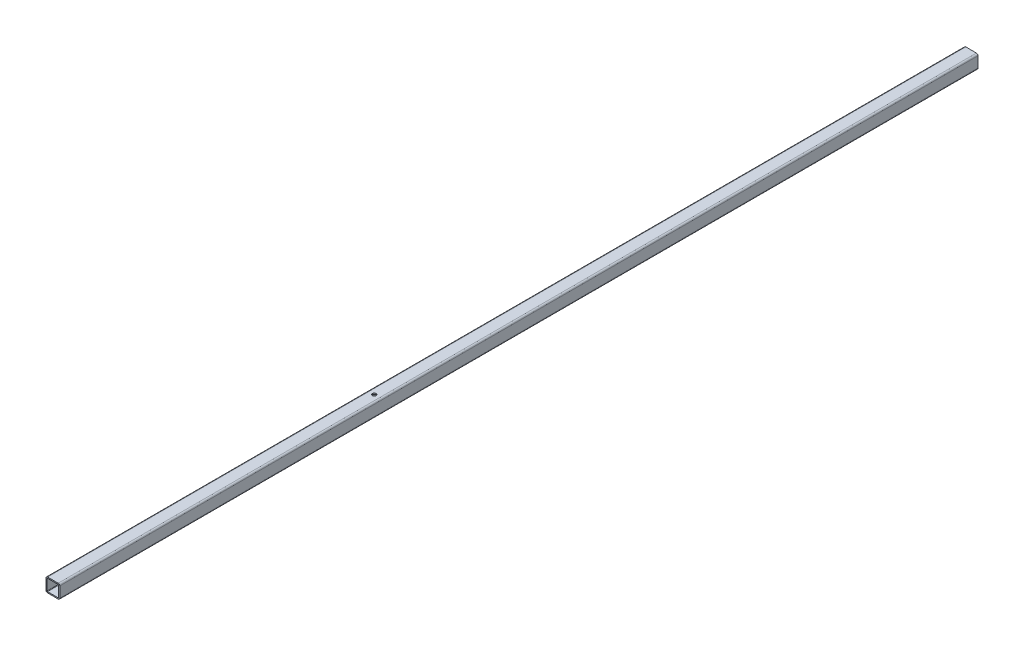
SolidWorks part; units mm, degrees
material "Plain Carbon Steel"
ref_plane "Front" through (0, 0, 0) normal (0, 0, 1) x (1, 0, 0)
ref_plane "Top" through (0, 0, 0) normal (0, 1, 0) x (1, 0, 0)
ref_plane "Right" through (0, 0, 0) normal (1, 0, 0) x (0, 0, -1)
ref_plane "Plane1" through (0, 0, 0) normal (0, 0, 1) x (1, 0, 0)
ref_axis "Axis1" through (0, 0, 62.7688) along (0, 0, -1)
ref_plane "Plane2" through (0, 0, 0) normal (-1, 0, 0) x (0, 0, 1)
ref_plane "Plane3" through (0, 0, 0) normal (0, -1, 0) x (1, 0, 0)
sketch "Sketch1" plane through (0, 0, 0) normal (0, 0, 1) x (1, 0, 0)
  line L0 (0, 0) -> (0, 43.8248) construction
  line L1 (-7.5, 7.5) -> (7.5, 7.5) construction
  line L2 (-7.5, 7.5) -> (-7.5, -7.5) construction
  line L3 (-7.5, -7.5) -> (7.5, -7.5) construction
  line L4 (7.5, 7.5) -> (7.5, -7.5) construction
  line L5 (0, 0) -> (51.9287, 0) construction
  line L6 (-6.3, 6.3) -> (-6.3, 7.5) construction
  line L7 (-6.3, 6.3) -> (6.3, 6.3) construction
  line L8 (-6.3, 6.3) -> (-6.3, -6.3) construction
  line L9 (-6.3, -6.3) -> (6.3, -6.3) construction
  line L10 (6.3, 6.3) -> (6.3, -6.3) construction
  line L11 (6.3, -6.3) -> (6.3, -7.5) construction
  line L12 (-6.3, 6.3) -> (-7.5, 6.3) construction
  line L13 (6.3, -6.3) -> (7.5, -6.3) construction
  line L14 (-5.8, 7.5) -> (5.8, 7.5)
  line L15 (-7.5, 5.8) -> (-7.5, -5.8)
  line L16 (7.5, 5.8) -> (7.5, -5.8)
  line L17 (-5.8, -7.5) -> (5.8, -7.5)
  line L18 (-6.3, 5.8) -> (-6.3, -5.8)
  line L20 (-5.8, -6.3) -> (5.8, -6.3)
  line L22 (6.3, -5.8) -> (6.3, 5.8)
  line L24 (5.8, 6.3) -> (-5.8, 6.3)
  arc A0 (-5.8, 7.5) -> (-7.5, 5.8) centre (-5.8, 5.8) ccw
  arc A1 (-7.5, -5.8) -> (-5.8, -7.5) centre (-5.8, -5.8) ccw
  arc A2 (5.8, 7.5) -> (7.5, 5.8) centre (5.8, 5.8) cw
  arc A3 (5.8, -7.5) -> (7.5, -5.8) centre (5.8, -5.8) ccw
  arc A4 (-6.3, 5.8) -> (-5.8, 6.3) centre (-5.8, 5.8) cw
  arc A5 (5.8, 6.3) -> (6.3, 5.8) centre (5.8, 5.8) cw
  arc A6 (5.8, -6.3) -> (6.3, -5.8) centre (5.8, -5.8) ccw
  arc A7 (-5.8, -6.3) -> (-6.3, -5.8) centre (-5.8, -5.8) cw
  point P7 (0, 7.5)
  point P9 (7.5, 0)
  point P20 (0, 7.5)
  point P23 (-7.5, 0)
  point P32 (0, -7.5)
  point P35 (0, 6.3)
  point P42 (6.3, 0)
  point P43 (-6.3, 0)
  point P44 (0, -6.3)
  dimension "D4" = 1.7
  dimension "D5" = 0.5
  dimension "D6" = 1.2
  dimension "D7" = 1.7
  dimension "D8" = 0.5
  dimension "D9" = 0.5
  dimension "D1" = 90
  dimension "D2" = 15
  dimension "D3" = 1.2
extrude "Extrude1" add sketch "Sketch1" along normal blind 1000
ref_plane "Plane4" through (0, 0, 1000) normal (0, 0, 1) x (1, 0, 0)
ref_plane "Plane5" through (0, 0, 0) normal (0, 0, -1) x (-1, 0, 0)
sketch "Sketch2" plane through (-7.5, 0, 0) normal (-1, 0, 0) x (0, 0, 1)
  line L0 (1000, 0) -> (697, 0) construction
  line L1 (1000, 5.8) -> (1000, -5.8) construction
  circle A0 centre (697, 0) radius 2
  dimension "D1" = 4
  dimension "D2" = 303
extrude "Cut-Extrude1" cut sketch "Sketch2" against normal blind 2
sketch "Sketch3" plane through (0, 7.5, 0) normal (0, 1, 0) x (-1, 0, 0)
  line L0 (0, 1000) -> (0, 650) construction
  line L1 (-5.8, 1000) -> (5.8, 1000) construction
  circle A0 centre (0, 650) radius 2
  dimension "D1" = 4
  dimension "D2" = 350
extrude "Cut-Extrude2" cut sketch "Sketch3" against normal blind 2
ref_plane "Plane6" [suppressed] through (-7.5, 0, 0) normal (-1, 0, 0) x (0, 0, 1)
